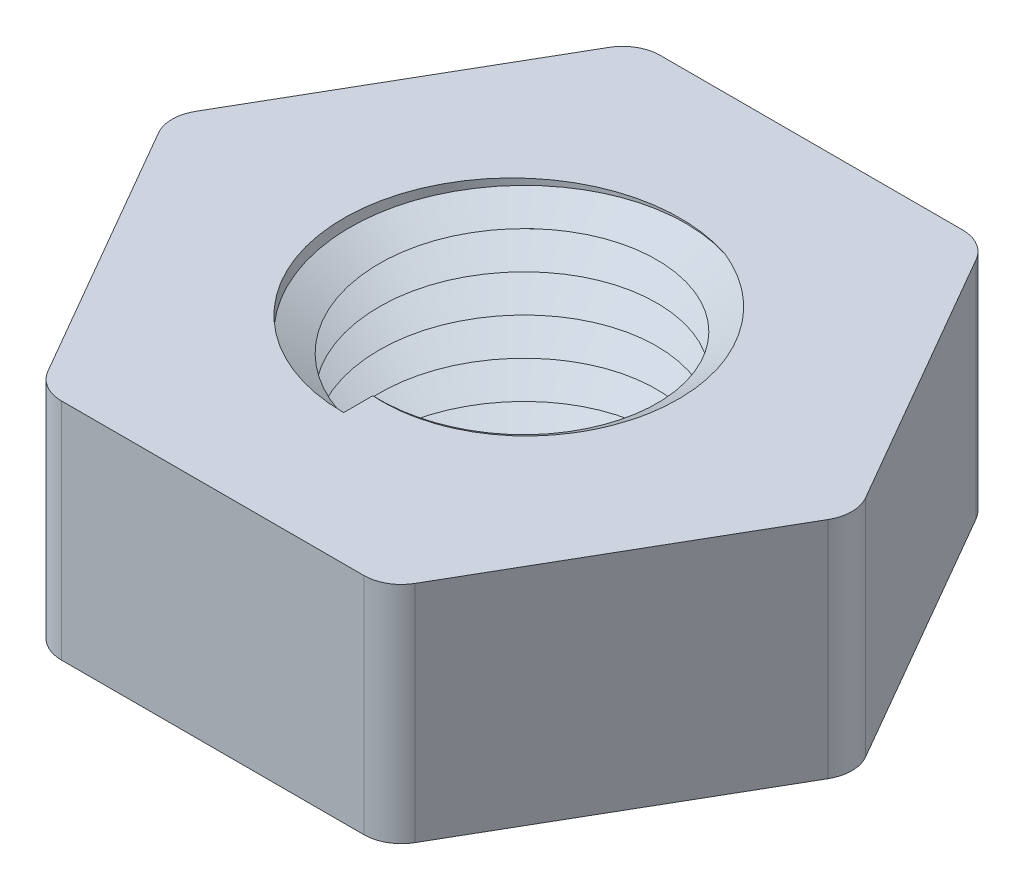
SolidWorks part; units mm, degrees
ref_plane "Front Plane" through (0, 0, 0) normal (0, 0, 1) x (1, 0, 0)
ref_plane "Top Plane" through (0, 0, 0) normal (0, 1, 0) x (1, 0, 0)
ref_plane "Right Plane" through (0, 0, 0) normal (1, 0, 0) x (0, 0, -1)
sketch "Sketch1" plane through (0, 0, 0) normal (0, 1, 0) x (1, 0, 0)
  line L1 (2.3094, -4) -> (4.6188, 0)
  line L2 (4.6188, 0) -> (2.3094, 4)
  line L3 (2.3094, 4) -> (-2.3094, 4)
  line L4 (-2.3094, 4) -> (-4.6188, 0)
  line L5 (-4.6188, 0) -> (-2.3094, -4)
  line L6 (-2.3094, -4) -> (2.3094, -4)
  circle A0 centre (0, 0) radius 4 construction
  dimension "D1" = 8
extrude "Boss-Extrude1" add sketch "Sketch1" along normal blind 3
sketch "Sketch2" plane through (0, 3, 0) normal (0, 1, 0) x (1, 0, 0)
  circle A0 centre (0, 0) radius 2.25
  dimension "D1" = 4.5
extrude "Cut-Extrude1" cut sketch "Sketch2" against normal through all
fillet "Fillet1" radius 0.5 6 edges at (4.6188, 1.5, 0) (2.3094, 1.5, -4) (-2.3094, 1.5, -4) (-4.6188, 1.5, 0) (-2.3094, 1.5, 4) (2.3094, 1.5, 4)
sketch "Sketch4" plane through (0, 3, 0) normal (0, 1, 0) x (1, 0, 0)
  circle A0 centre (0, 0) radius 2
  dimension "D1" = 4
curve "Helix/Spiral1" pitch 0.5 height 3 turns 6
sketch "Sketch5" plane through (0, 0, 0) normal (1, 0, 0) x (0, 0, -1)
  line L1 (-2.25, 2.775) -> (-1.8603, 3)
  line L2 (-1.8603, 3) -> (-2.25, 3.225)
  line L3 (-2.25, 3.225) -> (-2.25, 2.775)
  circle A0 centre (-2.1201, 3) radius 0.1299 construction
  point P1 (-2.25, 3)
  dimension "D1" = 0.45
sweep "Sweep3" add profiles "Sketch5" path "Helix/Spiral1"
ref_plane "Plane1" through (0, 3, 0) normal (0, 1, 0) x (1, 0, 0)
other "SurfaceCut1"
ref_plane "Plane2" through (0, 0, 0) normal (0, -1, 0) x (-1, 0, 0)
other "SurfaceCut2"
